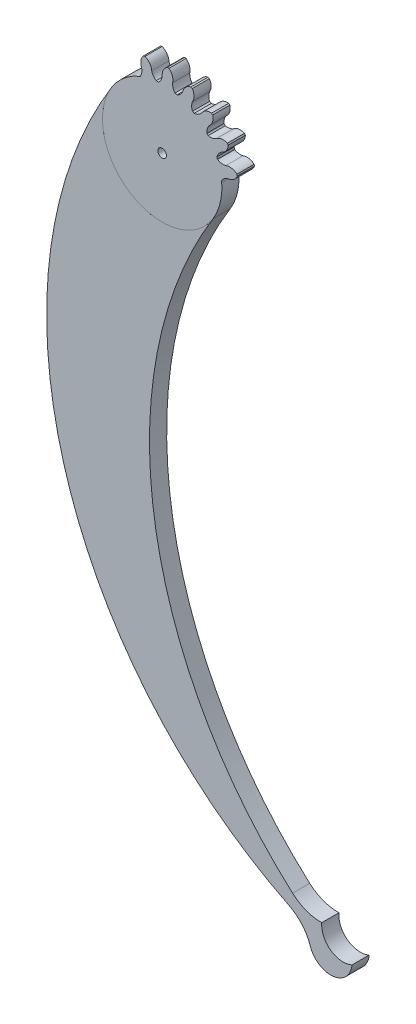
SolidWorks part; units mm, degrees
ref_plane "Plan de face" through (0, 0, 0) normal (0, 0, 1) x (1, 0, 0)
ref_plane "Plan de dessus" through (0, 0, 0) normal (0, 1, 0) x (1, 0, 0)
ref_plane "Plan de droite" through (0, 0, 0) normal (1, 0, 0) x (0, 0, -1)
sketch "Esquisse1" plane through (0, 0, 0) normal (0, 0, 1) x (1, 0, 0)
  circle A0 centre (0, 0) radius 18
extrude "Boss.-Extru.1" add sketch "Esquisse1" along normal blind 4
sketch "Esquisse3" plane through (0, 0, 4) normal (0, 0, 1) x (1, 0, 0)
  line L0 (-5.4964, 12.79) -> (-5.1005, 12.9694)
  line L1 (-1.4153, 13.9392) -> (-0.828, 13.9392)
  line L2 (3.4609, 13.4999) -> (2.9859, 13.6442)
  line L3 (7.0639, 12.0036) -> (7.4657, 11.7813)
  line L4 (10.417, 9.2257) -> (10.7311, 8.9116)
  line L5 (12.9063, 5.2048) -> (12.7653, 5.634)
  line L6 (13.8895, 0.9713) -> (13.8895, 1.4478)
  arc A0 (-7.2352, 14.2707) -> (15.9996, 0.1072) centre (0, 0) ccw
  arc A2 (3.4609, 13.4999) -> (4.9239, 15.2235) centre (2.4924, 15.8047) ccw
  arc A3 (7.0585, 13.9223) -> (7.2352, 14.2707) centre (4.9239, 15.2235) ccw
  arc A4 (7.4657, 11.7813) -> (9.3698, 12.9694) centre (7.2352, 14.2707) ccw
  arc A5 (11.0004, 11.0744) -> (9.4294, 15.4687) centre (9.3698, 12.9694) ccw
  arc A6 (10.7311, 8.9116) -> (12.9063, 9.4565) centre (11.2757, 11.3516) ccw
  arc A7 (13.8747, 7.1517) -> (13.7322, 11.8162) centre (12.9063, 9.4565) ccw
  arc A8 (12.9063, 5.2048) -> (15.1902, 5.0258) centre (14.2219, 7.3307) ccw
  arc A9 (-0.828, 13.9392) -> (0, 16) centre (-2.4924, 15.8047) ccw
  arc A10 (-2.4315, 15.4188) -> (-6.9047, 16.7487) centre (-4.9239, 15.2235) ccw
  arc A11 (-5.1005, 12.9694) -> (-4.9239, 15.2235) centre (-7.2352, 14.2707) ccw
  arc A12 (-7.0585, 13.9223) -> (-9.4294, 15.4687) centre (-9.3698, 12.9694) ccw
  arc A13 (15.4022, 2.5348) -> (16.7021, 7.0168) centre (15.1902, 5.0258) ccw
  arc A14 (13.8895, 0.9713) -> (15.9996, 0.1072) centre (15.7876, 2.5982) ccw
  arc A15 (15.7876, 2.5982) -> (13.8895, 1.4478) centre (15.9996, 0.1072) ccw
  arc A16 (18.0699, -1.2942) -> (15.609, 0.1046) centre (15.821, -2.3864) ccw
  arc A17 (-7.2352, 14.2707) -> (-5.4964, 12.79) centre (-4.9239, 15.2235) ccw
  arc A18 (-6.9047, 16.7487) -> (-9.4294, 15.4687) centre (-7.2352, 14.2707) ccw
  arc A19 (-2.4924, 15.8047) -> (-1.4153, 13.9392) centre (0, 16) ccw
  arc A20 (-1.4153, 18.0608) -> (-4.8037, 14.8519) centre (-2.4924, 15.8047) ccw
  arc A21 (-2.4924, 15.8047) -> (-4.9239, 15.2235) centre (0, 0) ccw
  arc A22 (1.4153, 18.0608) -> (-1.4153, 18.0608) centre (0, 16) ccw
  arc A24 (7.0585, 13.9223) -> (4.2114, 17.6199) centre (4.9239, 15.2235) ccw
  arc A25 (3.4609, 13.4999) -> (4.9239, 15.2235) centre (2.4924, 15.8047) ccw
  arc A26 (-2.4924, 15.8047) -> (-1.4153, 13.9392) centre (0, 16) ccw
  arc A27 (2.4315, 15.4188) -> (-1.4153, 18.0608) centre (0, 16) ccw
  arc A28 (2.4924, 15.8047) -> (2.9859, 13.6442) centre (4.9239, 15.2235) ccw
  arc A29 (4.2114, 17.6199) -> (0, 15.6094) centre (2.4924, 15.8047) ccw
  arc A30 (4.2114, 17.6199) -> (0, 15.6094) centre (2.4924, 15.8047) ccw
  arc A31 (2.4924, 15.8047) -> (0, 16) centre (0, 0) ccw
  arc A32 (7.2352, 14.2707) -> (7.0639, 12.0036) centre (9.3698, 12.9694) ccw
  arc A33 (9.4294, 15.4687) -> (4.8037, 14.8519) centre (7.2352, 14.2707) ccw
  arc A34 (11.2757, 11.3516) -> (10.417, 9.2257) centre (12.9063, 9.4565) ccw
  arc A35 (13.7322, 11.8162) -> (9.1411, 12.6528) centre (11.2757, 11.3516) ccw
  arc A36 (7.2352, 14.2707) -> (4.9239, 15.2235) centre (0, 0) ccw
  arc A37 (11.2757, 11.3516) -> (9.3698, 12.9694) centre (0, 0) ccw
  arc A38 (14.2219, 7.3307) -> (12.7653, 5.634) centre (15.1902, 5.0258) ccw
  arc A39 (14.2219, 7.3307) -> (12.9063, 9.4565) centre (0, 0) ccw
  arc A40 (16.7021, 7.0168) -> (12.5913, 9.2257) centre (14.2219, 7.3307) ccw
  arc A41 (18.0509, 1.5363) -> (14.8193, 4.9031) centre (15.7876, 2.5982) ccw
  arc A42 (15.7876, 2.5982) -> (15.1902, 5.0258) centre (0, 0) ccw
  arc A43 (18.0699, -1.2942) -> (18.0509, 1.5363) centre (15.9996, 0.1072) ccw
  circle A44 centre (0, 0) radius 1
  circle A45 centre (0, 0) radius 13.9234
  point P38 (0, 0)
  circle M5 centre (0, 0) radius 18
extrude "Enlèv. mat.-Extru.3" cut sketch "Esquisse3" against normal through all contours A20 A12 A17 L0 A11 M5 | A20 A10 A18 A12 M5 | A29 A10 A19 L1 A9 M5 | A29 A22 A20 A10 M5 | A33 A27 A28 L2 A2 M5 | A33 A24 A29 A27 M5 | A35 A24 A3 A32 L3 A4 M5 | A35 A5 A33 A24 M5 | A40 A5 A34 L4 A6 M5 | A40 A7 A35 A5 M5 | A41 A7 A38 L5 A8 M5 | A41 A13 A40 A7 M5 | A16 A13 A15 L6 A14 M5 | A16 A43 A41 A13 M5 | A44 | A16 A0 A12 M5 | A45 A17 A0 A14 | A12 A17 | A14 A16
sketch "Esquisse4" plane through (0, 0, 4) normal (0, 0, 1) x (1, 0, 0)
  line L0 (7.2648, 11.8925) -> (0, 0) construction
  line L1 (7.0639, 12.0036) -> (7.4657, 11.7813) construction
  line L2 (0, 0) -> (-7.2927, -11.8607) construction
  line L3 (-11.8607, 7.2927) -> (0, 0) construction
  line L4 (0, 0) -> (11.8607, -7.2927) construction
  line L5 (11.8607, -7.2927) -> (251.5797, -154.6863) construction
  line L6 (39.3045, -141.3199) -> (97.0504, -59.6724) construction
  arc A0 (-5.4019, 12.8328) -> (13.8895, 0.9713) centre (0, 0) ccw construction
  circle A1 centre (97.0504, -59.6724) radius 100.0045
  circle A2 centre (74.7934, -45.9875) radius 101.7238
  circle A3 centre (39.3045, -141.3199) radius 5
  circle A4 centre (42.1916, -137.2377) radius 5
  point P16 (39.3045, -141.3199)
  arc M8 (-5.4019, 12.8328) -> (13.8895, 0.9713) centre (0, 0) ccw
  dimension "D1" = 90
extrude "Boss.-Extru.2" add sketch "Esquisse4" against normal blind 4 separate body contours A2 A1 M8 | A2 A3 A1 | A1 A3 A2 | A4 A3 A1 | A4 A1 A3 A2 | A4 A2 A3
fillet "Congé1" radius 10 2 edges at (35.2957, -138.3316, 2) (34.6629, -139.4609, 2)
